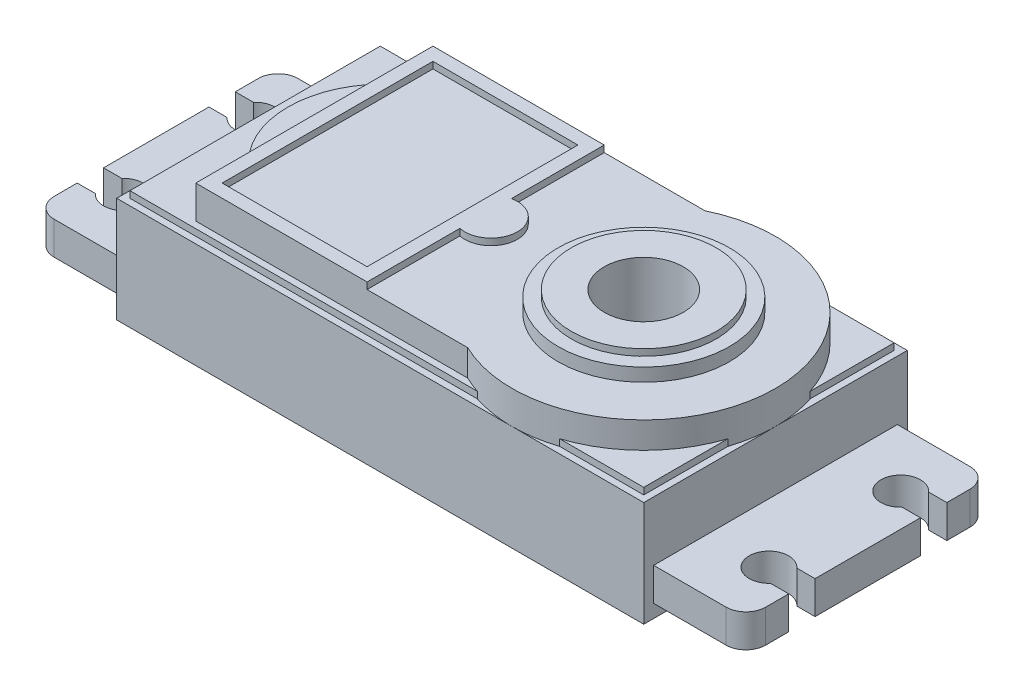
SolidWorks part; units mm, degrees
ref_plane "Piano frontale" through (0, 0, 0) normal (0, 0, 1) x (1, 0, 0)
ref_plane "Piano superiore" through (0, 0, 0) normal (0, 1, 0) x (1, 0, 0)
ref_plane "Piano destro" through (0, 0, 0) normal (1, 0, 0) x (0, 0, -1)
sketch "Schizzo1" plane through (0, 0, 0) normal (0, 1, 0) x (1, 0, 0)
  line L1 (20, -10) -> (-20, -10)
  line L2 (20, -10) -> (20, 10)
  line L3 (20, 10) -> (-20, 10)
  line L4 (-20, -10) -> (-20, 10)
  line L5 (20, -10) -> (-20, 10) construction
  line L6 (20, 10) -> (-20, -10) construction
  point P0 (0, 0)
  dimension "D1" = 20
  dimension "D2" = 40
extrude "Estrusione-Estrusione2" add sketch "Schizzo1" along normal blind 8
sketch "Schizzo2" plane through (0, 0, 0) normal (0, 1, 0) x (1, 0, 0)
  line L0 (-20, 10) -> (-20, -10) construction
  line L1 (16, -8) -> (-16, -8)
  line L2 (18, -6) -> (18, 6)
  line L3 (16, 8) -> (-16, 8)
  line L4 (-18, -6) -> (-18, 6)
  line L5 (16, -7.1111) -> (-16, 7.1111) construction
  line L6 (16, 7.1111) -> (-16, -7.1111) construction
  line L7 (20, 10) -> (-20, 10) construction
  line L8 (-16, 8) -> (-16, 6)
  line L9 (-16, 6) -> (-18, 6)
  line L10 (-18, -6) -> (-16, -6)
  line L11 (-16, -6) -> (-16, -8)
  line L12 (16, 8) -> (16, 6)
  line L13 (16, 6) -> (18, 6)
  line L14 (18, -6) -> (16, -6)
  line L15 (16, -6) -> (16, -8)
  point P0 (0, 0)
  dimension "D1" = 2
  dimension "D2" = 2
  dimension "D3" = 2
extrude "Taglio-Estrusione4" cut sketch "Schizzo2" along normal blind 6
hole_wizard "Foro per Vite M1-1" positions "Schizzo3D1" profile "Schizzo3" hole size "M1" standard "KS"
sketch3d "Schizzo3D1"
  line L0 (-20, 0, -10) -> (-20, 0, 10) construction
  line L1 (-20, 0, 10) -> (20, 0, 10) construction
  point P0 (-18, 0, 8)
  dimension "D1" = 2
  dimension "D2" = 2
sketch "Schizzo3" plane through (-18, 0, 8) normal (1, 0, 0) x (0, 0, -1)
  line L0 (0, 0) -> (0, 5.3906)
  line L1 (0, 5.3906) -> (0.65, 5)
  line L2 (0.65, 5) -> (0.65, 0.025)
  line L3 (0.65, 0.025) -> (0.675, 0)
  line L5 (0.675, 0) -> (0, 0)
  line L6 (-0.65, 0.025) -> (-0.675, 0) construction
  line L10 (0, 5.3906) -> (-0.65, 5) construction
  line L11 (0, -6.35) -> (0, 107.95) construction
  dimension "Hole Dia." = 1.3
  dimension "Hole Depth" = 5
  dimension "Near C'Sink Dia." = 1.35
  dimension "Near C'Sink Angle" = 90
  dimension "Drill Angle" = 118
mirror "Specchia1" about plane through (0, 0, 0) normal (1, 0, 0) of "Foro per Vite M1-1"
mirror "Specchia2" about plane through (0, 0, 0) normal (0, 0, 1) of "Specchia1"
sketch "Schizzo5" plane through (0, 0, 0) normal (0, -1, 0) x (1, 0, 0)
  line L0 (-20, -10) -> (-20, 10) construction
  line L1 (19, -9) -> (-19, -9)
  line L2 (19, -9) -> (19, 9)
  line L3 (19, 9) -> (-19, 9)
  line L4 (-19, -9) -> (-19, 9)
  line L5 (19, -9) -> (-19, 9) construction
  line L6 (19, 9) -> (-19, -9) construction
  line L7 (-20, 10) -> (20, 10) construction
  point P0 (0, 0)
  dimension "D1" = 1
  dimension "D2" = 1
sketch "Schizzo4" plane through (0, 0, 0) normal (0, 0, 1) x (1, 0, 0)
  line L0 (19, 0) -> (-19, 0) construction
  line L1 (19, 0) -> (-19, 0) construction
  line L2 (-20, 8) -> (-20, 0) construction
  line L3 (-19.25, 0) -> (-18.75, 0)
  arc A0 (-18.75, 0) -> (-19.25, 0) centre (-19, 0) ccw
  dimension "D1" = 0.5
  dimension "D2" = 1
sweep "Taglia-Sweep3" cut profiles "Schizzo4" path "Schizzo5"
sketch "Schizzo6" plane through (0, 8, 0) normal (0, 1, 0) x (1, 0, 0)
  line L0 (-20, 10) -> (-20, -10) construction
  line L1 (-15, 9) -> (5.6411, 9)
  line L2 (-15, 9) -> (-15, 5)
  line L3 (-15, -9) -> (11.8461, -9)
  line L5 (-15, 9) -> (11.8461, -9) construction
  line L6 (-15, -9) -> (11.8461, 9) construction
  line L7 (-20, -10) -> (20, -10) construction
  line L8 (20, 10) -> (-20, 10) construction
  line L9 (20, -10) -> (20, 10) construction
  line L10 (-15, -5) -> (-15, -9)
  arc A0 (5.6411, -9) -> (5.6411, 9) centre (10, 0) ccw
  arc A1 (-15, -5) -> (-15, 5) centre (-9.75, 0) cw
  point P0 (-1.5769, 0)
  point P19 (-17, 0)
  dimension "D1" = 5
  dimension "D2" = 1
  dimension "D3" = 1
  dimension "D4" = 10
  dimension "D5" = 2
extrude "Estrusione-Estrusione4" add sketch "Schizzo6" along normal blind 2.5 contours A1 L10 L3 A0 L1 L2 region at (1.5065, 8, 0)
sketch "Schizzo7" plane through (0, 8, 0) normal (0, 1, 0) x (1, 0, 0)
  line L0 (20, 10) -> (10, 10) construction
  line L1 (-19.5, -9.5) -> (19.5, -9.5)
  line L2 (-19.5, -9.5) -> (-19.5, 9.5)
  line L3 (-19.5, 9.5) -> (19.5, 9.5)
  line L4 (19.5, -9.5) -> (19.5, 9.5)
  line L5 (-19.5, -9.5) -> (19.5, 9.5) construction
  line L6 (-19.5, 9.5) -> (19.5, -9.5) construction
  line L7 (-20, 10) -> (-20, -10) construction
  point P0 (0, 0)
  dimension "D1" = 0.5
  dimension "D2" = 0.5
extrude "Estrusione-Estrusione3" add sketch "Schizzo7" along normal blind 0.5
sketch "Schizzo8" plane through (0, 10.5, 0) normal (0, 1, 0) x (1, 0, 0)
  line L0 (-15, -9) -> (5.6411, -9) construction
  line L1 (-15, 9) -> (-2, 9)
  line L2 (-15, 9) -> (-15, -9)
  line L3 (-15, -9) -> (-2, -9)
  line L4 (-2, 9) -> (-2, 1.9577)
  line L5 (-20, 10) -> (-20, -10) construction
  line L6 (-14, -8) -> (-3, -8)
  line L7 (-14, -8) -> (-14, 8)
  line L8 (-14, 8) -> (-3, 8)
  line L9 (-3, -8) -> (-3, 8)
  line L10 (-14, -8) -> (-3, 8) construction
  line L11 (-14, 8) -> (-3, -8) construction
  line L12 (-2, -1.9577) -> (-2, -9)
  arc A0 (-2, -1.9577) -> (-2, 1.9577) centre (-1.5909, 0) ccw
  point P7 (-8.5, 0)
  dimension "D6" = 4
  dimension "D7" = 18.4091
  dimension "D1" = 1
  dimension "D2" = 1
  dimension "D3" = 1
  dimension "D4" = 1
  dimension "D5" = 13
extrude "Estrusione-Estrusione5" add sketch "Schizzo8" along normal blind 0.5
sketch "Schizzo9" plane through (0, 10.5, 0) normal (0, 1, 0) x (1, 0, 0)
  circle A0 centre (10, 0) radius 6.5
  dimension "D1" = 13
extrude "Estrusione-Estrusione6" add sketch "Schizzo9" along normal blind 1
sketch "Schizzo10" plane through (0, 11.5, 0) normal (0, 1, 0) x (1, 0, 0)
  circle A0 centre (10, 0) radius 5.5
  dimension "D1" = 11
extrude "Estrusione-Estrusione7" add sketch "Schizzo10" along normal blind 0.5
sketch "Schizzo11" plane through (0, 12, 0) normal (0, 1, 0) x (1, 0, 0)
  circle A0 centre (10, 0) radius 3
  dimension "D1" = 6
extrude "Taglio-Estrusione5" cut sketch "Schizzo11" against normal through all
ref_plane "Piano1" through (0, 1, 0) normal (0, -1, 0) x (-1, 0, 0)
sketch "Schizzo12" plane through (0, 1, 0) normal (0, -1, 0) x (-1, 0, 0)
  line L0 (-20, -10) -> (-20, 10) construction
  line L2 (-25.5, 9.25) -> (-20, 9.25)
  line L3 (-27, 7.75) -> (-27, -7.75)
  line L4 (-25.5, -9.25) -> (-20, -9.25)
  line L5 (-20, 9.25) -> (-20, -9.25)
  line L6 (-27, 9.25) -> (-20, -9.25) construction
  line L7 (-27, -9.25) -> (-20, 9.25) construction
  arc A0 (-25.5, -9.25) -> (-27, -7.75) centre (-25.5, -7.75) cw
  arc A1 (-27, 7.75) -> (-25.5, 9.25) centre (-25.5, 7.75) cw
  circle A2 centre (-24.5, 5) radius 1.5
  circle A3 centre (-24.5, -5) radius 1.5
  point P0 (-23.5, 0)
  dimension "D3" = 1.5
  dimension "D4" = 3
  dimension "D1" = 18.5
  dimension "D2" = 7
  dimension "D5" = 10
  dimension "D6" = 2.5
  dimension "D7" = 5
extrude "Estrusione-Estrusione8" add sketch "Schizzo12" against normal blind 2.5
sketch "Schizzo13" plane through (0, 3.5, 0) normal (0, 1, 0) x (1, 0, 0)
  line L1 (30.9082, -5.9404) -> (24.8886, -5.9404)
  line L2 (30.9082, -5.9404) -> (30.9082, -4.9899)
  line L3 (30.9082, -4.9899) -> (24.8886, -4.9899)
  line L4 (24.8886, -5.9404) -> (24.8886, -4.9899)
  line L5 (30.9082, -5.9404) -> (24.8886, -4.9899) construction
  line L6 (30.9082, -4.9899) -> (24.8886, -5.9404) construction
  line L7 (34.3221, 4) -> (25.3835, 4)
  line L8 (34.3221, 4) -> (34.3221, 6)
  line L9 (34.3221, 6) -> (25.3835, 6)
  line L10 (25.3835, 4) -> (25.3835, 6)
  line L11 (34.3221, 4) -> (25.3835, 6) construction
  line L12 (34.3221, 6) -> (25.3835, 4) construction
  circle A0 centre (24.5, 5) radius 1.5 construction
  arc A1 (25.618, 4) -> (25.6727, 4.0647) centre (24.5, 5) ccw
  arc A2 (25.6727, 5.9353) -> (25.618, 6) centre (24.5, 5) ccw
  point P0 (27.8984, -5.4652)
  point P5 (29.8528, 5)
  circle M8 centre (24.5, 5) radius 1.5
  line M12 (27, -7.75) -> (27, 7.75)
  dimension "D1" = 2
  dimension "D2" = 8.9386
extrude "Taglio-Estrusione6" cut sketch "Schizzo13" against normal through all contours L8 L9 L7 M12 | L9 L7 M12 M8 region at (26.4345, 3.5, -5) region at (30.661, 3.5, -5)
mirror "Specchia3" about plane through (0, 0, 0) normal (0, 0, 1) of "Taglio-Estrusione6"
mirror "Specchia4" about plane through (0, 0, 0) normal (1, 0, 0) of "Specchia3", "Taglio-Estrusione6", "Estrusione-Estrusione8"
